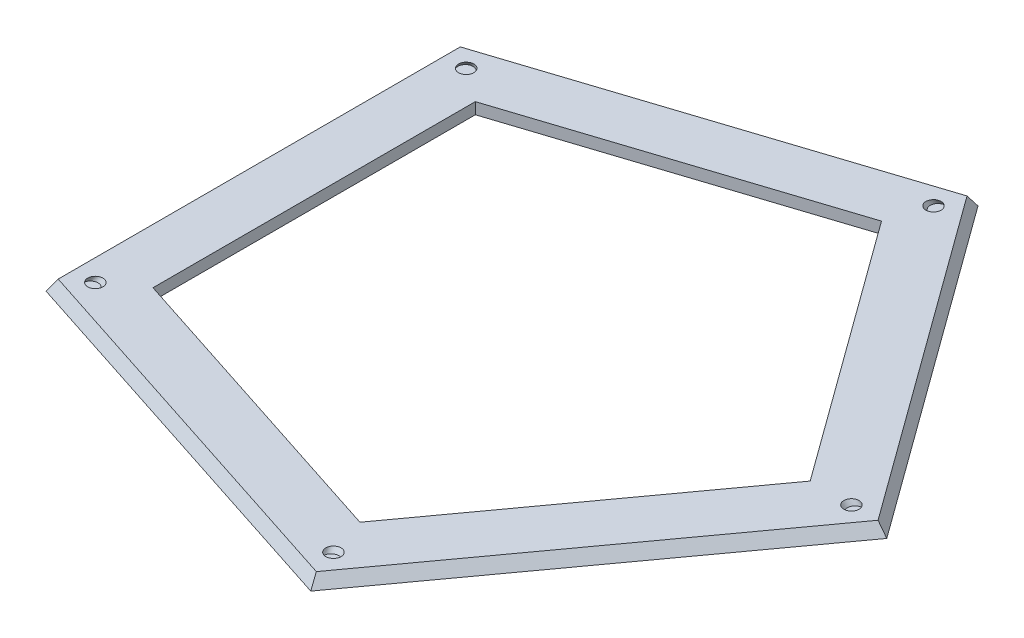
SolidWorks part; units mm, degrees
ref_plane "Front Plane" through (0, 0, 0) normal (0, 0, 1) x (1, 0, 0)
ref_plane "Top Plane" through (0, 0, 0) normal (0, 1, 0) x (1, 0, 0)
ref_plane "Right Plane" through (0, 0, 0) normal (1, 0, 0) x (0, 0, -1)
sketch "Sketch1" plane through (0, 0, 0) normal (0, 1, 0) x (1, 0, 0)
  line L1 (92.2725, 0) -> (28.5138, 87.7563)
  line L2 (28.5138, 87.7563) -> (-74.65, 54.2364)
  line L3 (-74.65, 54.2364) -> (-74.65, -54.2364)
  line L4 (-74.65, -54.2364) -> (28.5138, -87.7563)
  line L5 (28.5138, -87.7563) -> (92.2725, 0)
  circle A0 centre (0, 0) radius 74.65 construction
extrude "Boss-Extrude1" add sketch "Sketch1" along normal blind 3 contours L5 L1 L2 L3 L4
chamfer "Chamfer1" distance 3 angle 31.715 5 edges at (-74.65, 3, 0) (-23.0681, 3, -70.9964) (60.3931, 3, -43.8782) (60.3931, 3, 43.8782) (-23.0681, 3, 70.9964)
sketch3d "3DSketch1"
  line L0 (-58.35, 0, -42.3938) -> (-58.35, 0, 42.3938)
  line L1 (22.2877, 0, -68.5945) -> (-58.35, 0, -42.3938)
  line L2 (72.1246, 0, 0) -> (22.2877, 0, -68.5945)
  line L3 (22.2877, 0, 68.5945) -> (72.1246, 0, 0)
  line L4 (-58.35, 0, 42.3938) -> (22.2877, 0, 68.5945)
  line L5 (-58.35, 0, -42.3938) -> (-58.35, 0, 42.3938)
  line L6 (22.2877, 0, -68.5945) -> (-58.35, 0, -42.3938)
  line L7 (72.1246, 0, 0) -> (22.2877, 0, -68.5945)
  line L8 (22.2877, 0, 68.5945) -> (72.1246, 0, 0)
  line L9 (-58.35, 0, 42.3938) -> (22.2877, 0, 68.5945)
  dimension "D1" = 16.3
extrude "Cut-Extrude1" cut sketch "3DSketch1" along direction (0, 1, 0) on the side against the normal blind 10 contours L5 L9 L8 L7 L6
sketch "Sketch2" plane through (0, 3, 0) normal (0, 1, 0) x (1, 0, 0)
  line L0 (-72.7961, 52.8894) -> (-58.35, 42.3938) construction
  line L1 (-72.7961, 52.8894) -> (-67.133, 48.7749)
  circle A2 centre (-67.133, 48.7749) radius 2
sketch "Sketch5" plane through (0, 3, 0) normal (0, 1, 0) x (1, 0, 0)
  line L0 (27.8056, 85.5769) -> (22.2877, 68.5945) construction
  line L1 (27.8056, 85.5769) -> (25.6425, 78.9195)
  circle A2 centre (25.6425, 78.9195) radius 2
sketch "Sketch9" plane through (0, 3, 0) normal (0, 1, 0) x (1, 0, 0)
  line L0 (89.9809, 0) -> (72.1246, 0) construction
  line L1 (89.9809, 0) -> (82.9809, 0)
  circle A1 centre (82.9809, 0) radius 2
sketch "Sketch10" plane through (0, 3, 0) normal (0, 1, 0) x (1, 0, 0)
  line L0 (22.2877, -68.5945) -> (27.8056, -85.5769) construction
  line L1 (27.8056, -85.5769) -> (25.6425, -78.9195)
  circle A1 centre (25.6425, -78.9195) radius 2
sketch "Sketch11" plane through (0, 3, 0) normal (0, 1, 0) x (1, 0, 0)
  line L0 (-58.35, -42.3938) -> (-72.7961, -52.8894) construction
  line L1 (-72.7961, -52.8894) -> (-67.133, -48.7749)
  circle A1 centre (-67.133, -48.7749) radius 2
extrude "Cut-Extrude2" cut sketch "Sketch2" along direction (0.4911, 0.7947, 0.3568) on the side against the normal blind 1.5 contours A2
extrude "Cut-Extrude3" cut sketch "Sketch5" along direction (-0.1876, 0.7947, 0.5773) on the side against the normal blind 1.5 contours A2
extrude "Cut-Extrude4" cut sketch "Sketch9" along direction (-0.607, 0.7947, 0) on the side against the normal blind 1.5 contours A1
extrude "Cut-Extrude5" cut sketch "Sketch10" along direction (-0.1876, 0.7947, -0.5773) on the side against the normal blind 1.5 contours A1
extrude "Cut-Extrude6" cut sketch "Sketch11" along direction (-0.4911, -0.7947, 0.3568) on the side against the normal blind 1.5 contours A1
